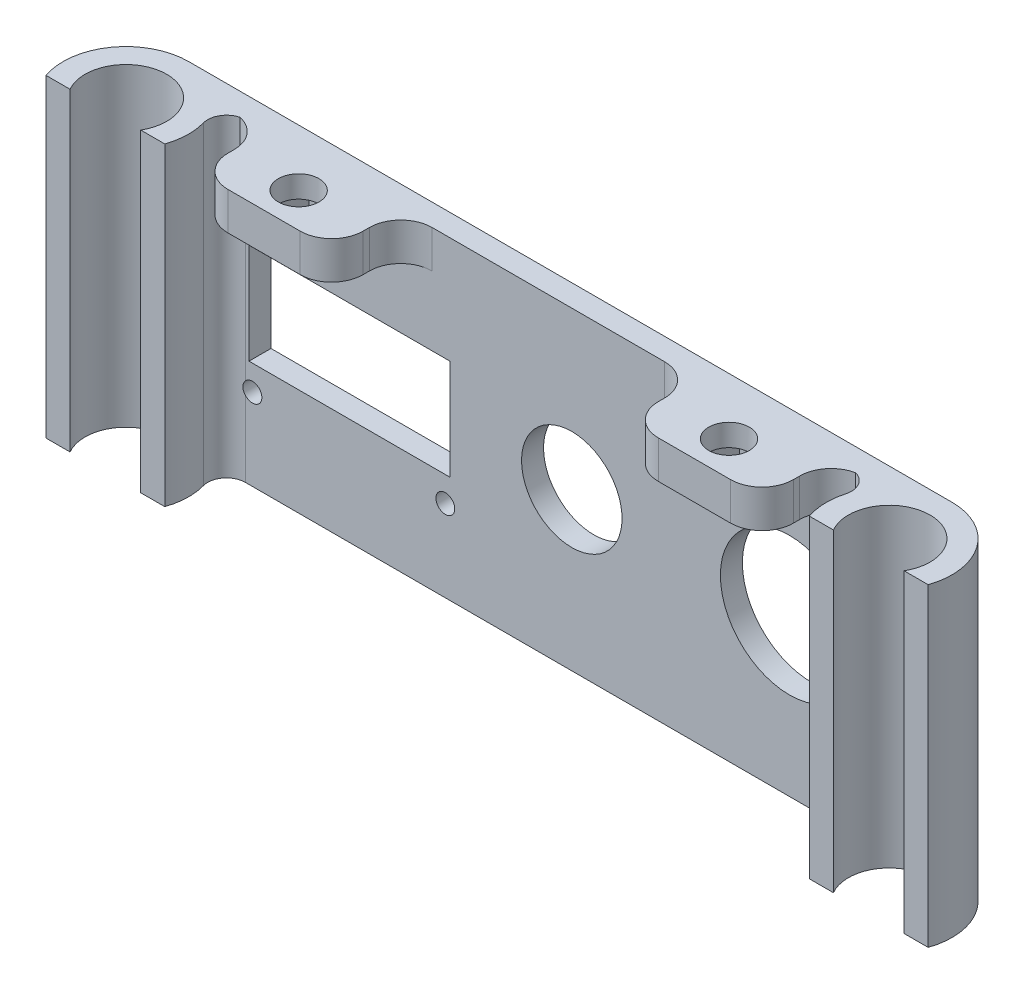
SolidWorks part; units mm, degrees
ref_plane "Front Plane" through (0, 0, 0) normal (0, 0, 1) x (1, 0, 0)
ref_plane "Top Plane" through (0, 0, 0) normal (0, 1, 0) x (1, 0, 0)
ref_plane "Right Plane" through (0, 0, 0) normal (1, 0, 0) x (0, 0, -1)
sketch "Sketch1" plane through (0, 0, 0) normal (0, 1, 0) x (1, 0, 0)
  line L0 (0, 0) -> (-121.5, 0)
  line L1 (-121.5, 10) -> (0, 10)
  line L2 (0, 10) -> (0, 6.5)
  line L3 (0, 6.5) -> (-121.5, 6.5)
  line L4 (-121.5, 0) -> (-121.5, -1.3505)
  line L5 (-121.5, -1.3505) -> (-137.3585, -1.3505)
  line L6 (-137.3585, -1.3505) -> (23.118, -1.3505)
  circle A0 centre (-121.5, 0) radius 6.5
  circle A1 centre (0, 0) radius 6.5
  circle A2 centre (-121.5, 0) radius 10
  circle A3 centre (0, 0) radius 10
extrude "Boss-Extrude2" add sketch "Sketch1" along normal blind 50 contours L6 A3 L2 A1 | L2 A3 L3 | A3 L1 A2 L3 | L3 A3 L0 A1 | L0 A3 L6 A1 | L0 A2 L3 A0 | L3 A2 L6 A0 region at (-114.5212, 0, -3.5511) region at (-6.9788, 0, -3.5511) region at (-8.2111, 0, 0.6768) region at (-60.75, 0, -8.2811) region at (-124.8059, 0, -5.6129) region at (-2.9305, 0, -7.9234) region at (5.6039, 0, -4.7615)
sketch "Sketch2" plane through (0, 50, 0) normal (0, 1, 0) x (1, 0, 0)
  line L0 (-60.75, 6.5) -> (-60.75, -4.5)
  line L1 (-60.75, -4.5) -> (-105.75, -4.5)
  line L2 (-7.5993, 6.5) -> (-113.9007, 6.5) construction
  line L3 (-60.75, -4.5) -> (-15.75, -4.5)
  line L4 (-105.75, -4.5) -> (-105.75, 6.5)
  line L5 (-105.75, 6.5) -> (-15.75, 6.5)
  line L6 (-15.75, 6.5) -> (-15.75, -4.5)
  line L7 (-115, 0) -> (-95, 0)
  line L8 (-6.5, 0) -> (-26.5, 0)
  line L9 (-95, 6.5) -> (-95, -4.5)
  line L10 (-26.5, 6.5) -> (-26.5, -4.5)
  line L11 (-105.75, -4.5) -> (-95, -4.5)
  line L12 (-95, -4.5) -> (-84.25, -4.5)
  line L13 (-26.5, -4.5) -> (-37.25, -4.5)
  line L14 (-37.25, -4.5) -> (-37.25, 6.5)
  line L15 (-37.25, 6.5) -> (-84.25, 6.5)
  line L16 (-84.25, 6.5) -> (-84.25, -4.5)
  line L17 (-131.4084, -1.3505) -> (-107.8559, -1.3505)
  arc A0 (6.3582, -1.3505) -> (-6.3582, -1.3505) centre (0, 0) ccw construction
  circle A3 centre (-95, 1) radius 3
  circle A4 centre (-26.5, 1) radius 3
  circle A5 centre (-121.5, 0) radius 6.5
  circle A6 centre (-121.5, 0) radius 10
  line M14 (-115, 0) -> (-111.5, 0)
  line M16 (-113.9007, 6.5) -> (-7.5993, 6.5)
extrude "Boss-Extrude3" add sketch "Sketch2" against normal blind 6 contours A3 L9 L1 L16 L5 | A3 L7 L4 L1 L9 | A3 L9 L4 L7 M16 | A4 L10 L5 L14 L3 | A4 L8 L6 L5 L10 | A4 L10 L3 L6 L8 | L17 A6 A5 M14 region at (-89.068, 50, -1) region at (-32.432, 50, -1) region at (-101.0512, 50, -3.5003) region at (-20.4488, 50, -3.5003) region at (-100.7706, 50, 2.3825) region at (-20.7294, 50, 2.3825) region at (-113.2889, 50, 0.6768)
sketch "Sketch3" plane through (0, 44, 0) normal (0, -1, 0) x (1, 0, 0)
  line L2 (-111.5916, 1.3505) -> (-115.1418, 1.3505)
  line L3 (-115, 0) -> (-111.5, 0)
  line L4 (-111.5916, 1.3505) -> (-115.1418, 1.3505)
  line L5 (-115, 0) -> (-111.5, 0)
  arc A2 (-115, 0) -> (-115.1418, 1.3505) centre (-121.5, 0) ccw
  arc A3 (-111.5, 0) -> (-111.5916, 1.3505) centre (-121.5, 0) ccw
  arc A4 (-115, 0) -> (-115.1418, 1.3505) centre (-121.5, 0) ccw
  arc A5 (-111.5, 0) -> (-111.5916, 1.3505) centre (-121.5, 0) ccw
  dimension "D1" = 0
extrude "Boss-Extrude4" add sketch "Sketch3" along normal up to surface (44 mm away) up to face at (-60.8146, 0, -3.7377)
fillet "Fillet1" radius 5 8 edges at (-105.75, 47, -6.5) (-84.25, 47, -6.5) (-37.25, 47, -6.5) (-15.75, 47, -6.5) (-15.75, 47, 4.5) (-37.25, 47, 4.5) (-84.25, 47, 4.5) (-105.75, 47, 4.5)
fillet "Fillet2" radius 3 2 edges at (-7.5993, 25, -6.5) (-113.9007, 25, -6.5)
sketch "Sketch5" plane through (0, 44, 0) normal (0, -1, 0) x (1, 0, 0)
  line L1 (-21.8969, -1) -> (-24.1984, 2.9864)
  line L2 (-24.1984, 2.9864) -> (-28.8016, 2.9864)
  line L3 (-28.8016, 2.9864) -> (-31.1031, -1)
  line L4 (-31.1031, -1) -> (-28.8016, -4.9864)
  line L5 (-28.8016, -4.9864) -> (-24.1984, -4.9864)
  line L6 (-24.1984, -4.9864) -> (-21.8969, -1)
  line L7 (-90.4012, -1) -> (-92.7006, 2.9827)
  line L8 (-92.7006, 2.9827) -> (-97.2994, 2.9827)
  line L9 (-97.2994, 2.9827) -> (-99.5988, -1)
  line L10 (-99.5988, -1) -> (-97.2994, -4.9827)
  line L11 (-97.2994, -4.9827) -> (-92.7006, -4.9827)
  line L12 (-92.7006, -4.9827) -> (-90.4012, -1)
  circle A2 centre (-26.5, -1) radius 3.9864 construction
  circle A3 centre (-95, -1) radius 3.9827 construction
extrude "Cut-Extrude3" cut sketch "Sketch5" against normal blind 2.5
sketch "Sketch6" plane through (0, 0, -10) normal (0, 0, -1) x (-1, 0, 0)
  line L0 (0, 25) -> (121.5, 25)
  line L1 (76.4046, 17) -> (108.4046, 17)
  line L2 (76.4046, 17) -> (76.4046, 32.9891)
  line L3 (76.4046, 32.9891) -> (108.4046, 32.9891)
  line L4 (108.4046, 17) -> (108.4046, 32.9891)
  line L5 (0, 50) -> (0, 0) construction
  line L6 (121.5, 50) -> (121.5, 0) construction
  line L7 (108.4046, 32.9891) -> (108.4046, 17)
  line L8 (76.4046, 17) -> (76.4046, 0)
  line L9 (121.5, 0) -> (0, 0) construction
  line L10 (108.4046, 17) -> (108.4046, 13)
  line L11 (92.4046, 17) -> (92.4046, 13)
  line L12 (92.4046, 13) -> (107.8546, 13)
  line L13 (92.4046, 13) -> (77.1546, 13)
  circle A0 centre (22.3762, 25) radius 11
  circle A1 centre (57.0266, 25) radius 8
  circle A2 centre (22.3762, 25) radius 16
  circle A3 centre (57.0266, 25) radius 11
  circle A4 centre (107.8546, 13) radius 1.5
  circle A5 centre (77.1546, 13) radius 1.5
  circle A6 centre (22.3762, 25) radius 12.5
extrude "Cut-Extrude7" cut sketch "Sketch6" against normal blind 65 contours L0 L4 L3 L2 | L1 L4 L0 L2 | A4 | A5 L8 | L8 A5 | L0 A1 | L0 A1 | L0 A0 | L0 A0 region at (-22.3762, 20.3315, -10) region at (-22.3762, 29.6685, -10) region at (-92.4046, 28.9946, -10) region at (-92.4046, 21, -10) region at (-57.0266, 28.3953, -10) region at (-57.0266, 21.6047, -10) region at (-77.8859, 14.2666, -10) region at (-76.0971, 13, -10) region at (-109.0595, 13.8202, -10)
sketch "Sketch7" plane through (0, 0, -6.5) normal (0, 0, 1) x (1, 0, 0)
  circle A0 centre (-22.3762, 25) radius 14
extrude "Cut-Extrude8" cut sketch "Sketch7" along normal blind 50
sketch "Sketch8" plane through (0, 50, 0) normal (0, 1, 0) x (1, 0, 0)
  circle A0 centre (-95, 1) radius 3.15
  circle A1 centre (-26.5, 1) radius 3.15
extrude "Cut-Extrude9" cut sketch "Sketch8" against normal blind 10
sketch "Sketch9" plane through (0, 50, 0) normal (0, 1, 0) x (1, 0, 0)
  line L0 (-131.2801, -2.0856) -> (9.7801, -2.0856)
  circle A0 centre (-121.5, 0) radius 6.5
  circle A1 centre (-121.5, 0) radius 10
  circle A2 centre (0, 0) radius 6.5
  circle A3 centre (0, 0) radius 10
  line M10 (-9.9084, -1.3505) -> (-6.3582, -1.3505)
  line M12 (6.3582, -1.3505) -> (9.9084, -1.3505)
  line M16 (-131.4084, -1.3505) -> (-127.8582, -1.3505)
  line M18 (-115.1418, -1.3505) -> (-111.5916, -1.3505)
extrude "Boss-Extrude5" add sketch "Sketch9" against normal up to surface (50 mm away) contours A1 L0 A0 M16 | L0 A1 A0 M18 | A3 L0 A2 M10 | L0 A3 A2 M12 region at (-129.5567, 50, 1.7193) region at (-8.0567, 50, 1.7193) region at (-113.4433, 50, 1.7193) region at (8.0567, 50, 1.7193) up to face at (-60.75, 0, -3.5177)
sketch "Sketch10" plane through (0, 0, -6.5) normal (0, 0, 1) x (1, 0, 0)
  circle A0 centre (-22.3762, 25) radius 14
extrude "Cut-Extrude10" cut sketch "Sketch10" along normal blind 28
sketch "Sketch11" plane through (0, 0, 0) normal (0, -1, 0) x (1, 0, 0)
  line L0 (-130.9535, 3.2606) -> (9.4535, 3.2606)
  circle A0 centre (-121.5, 0) radius 10
  circle A1 centre (-121.5, 0) radius 6.5
  circle A2 centre (0, 0) radius 6.5
  circle A3 centre (0, 0) radius 10
  line M4 (9.7801, 2.0856) -> (6.1563, 2.0856)
  line M6 (-6.1563, 2.0856) -> (-9.7801, 2.0856)
  line M12 (-111.7199, 2.0856) -> (-115.3437, 2.0856)
  line M14 (-127.6563, 2.0856) -> (-131.2801, 2.0856)
extrude "Boss-Extrude6" add sketch "Sketch11" against normal up to surface (50 mm away) contours A3 L0 A2 M4 | L0 A3 A2 M6 | A1 A0 L0 M12 | A1 L0 A0 M14 region at (-129.2694, 0, 2.6785) region at (-7.7694, 0, 2.6785) region at (-113.7306, 0, 2.6785) region at (7.7694, 0, 2.6785) up to face at (-95, 50, 2.15)
sketch "Sketch12" plane through (0, 50, 0) normal (0, 1, 0) x (1, 0, 0)
  circle A0 centre (-95, 1) radius 3.23
  circle A1 centre (-26.5, 1) radius 3.23
extrude "Cut-Extrude11" cut sketch "Sketch12" against normal blind 10
